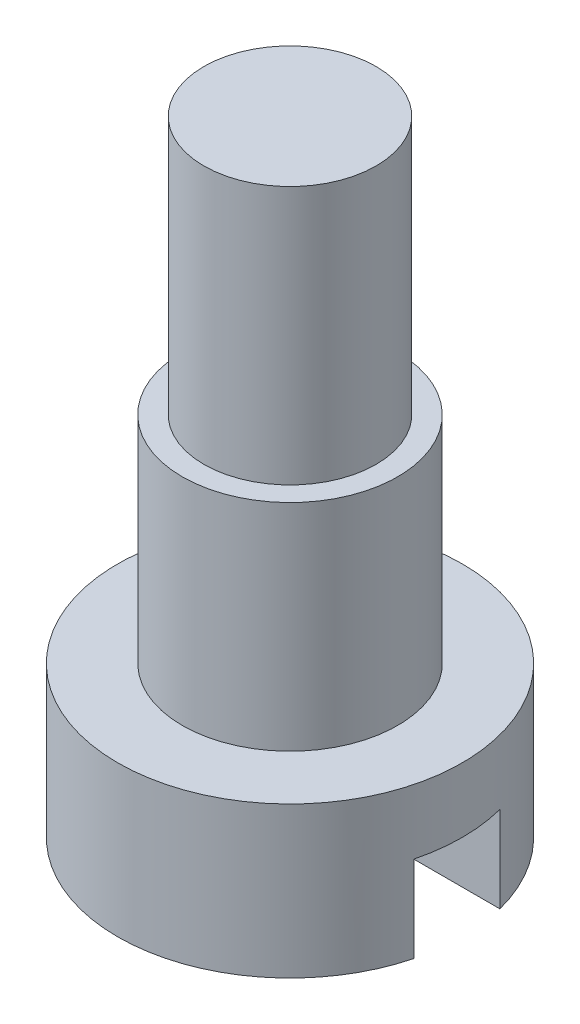
SolidWorks part; units mm, degrees
ref_plane "Front Plane" through (0, 0, 0) normal (0, 0, 1) x (1, 0, 0)
ref_plane "Top Plane" through (0, 0, 0) normal (0, 1, 0) x (1, 0, 0)
ref_plane "Right Plane" through (0, 0, 0) normal (1, 0, 0) x (0, 0, -1)
sketch "Sketch1" plane through (0, 0, 0) normal (0, 1, 0) x (1, 0, 0)
  circle A0 centre (0, 0) radius 8
  dimension "D1" = 16
extrude "Boss-Extrude1" add sketch "Sketch1" against normal blind 7
sketch "Sketch2" plane through (0, 0, 0) normal (0, 1, 0) x (1, 0, 0)
  circle A0 centre (0, 0) radius 5
  dimension "D1" = 10
extrude "Boss-Extrude2" add sketch "Sketch2" along normal blind 10
sketch "Sketch3" plane through (0, 0, 0) normal (1, 0, 0) x (0, 0, -1)
  line L0 (-2, -7) -> (-2, -3)
  line L1 (-8, -7) -> (8, -7) construction
  line L2 (-2, -3) -> (2, -3)
  line L3 (2, -3) -> (2, -7)
  line L4 (2, -7) -> (-2, -7)
  point P6 (0, -7)
  dimension "D1" = 4
  dimension "D2" = 4
extrude "Cut-Extrude1" cut sketch "Sketch3" against normal blind 10 and the other way blind 10
sketch "Sketch4" plane through (0, 10, 0) normal (0, 1, 0) x (1, 0, 0)
  circle A0 centre (0, 0) radius 4
  dimension "D1" = 8
extrude "Boss-Extrude3" add sketch "Sketch4" along normal blind 12
cosmetic thread "Cosmetic Thread1" parameters "D1"=10, "D2"=6.619
